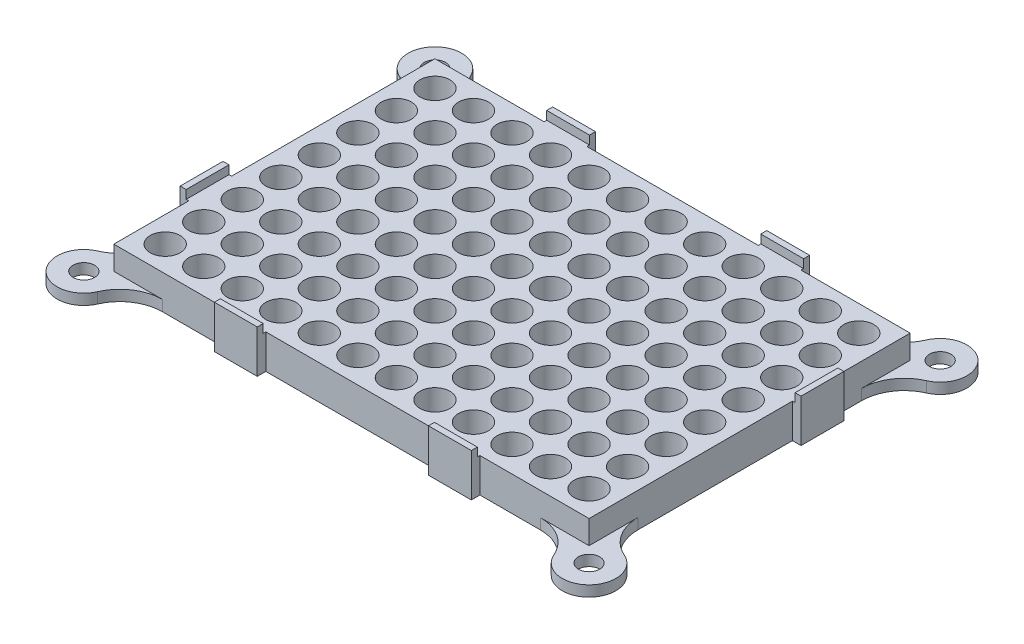
SolidWorks part; units mm, degrees
ref_plane "Front Plane" through (0, 0, 0) normal (0, 0, 1) x (1, 0, 0)
ref_plane "Top Plane" through (0, 0, 0) normal (0, 1, 0) x (1, 0, 0)
ref_plane "Right Plane" through (0, 0, 0) normal (1, 0, 0) x (0, 0, -1)
sketch "Sketch3" plane through (0, 0, 0) normal (0, 1, 0) x (1, 0, 0)
  line L0 (64, 80.5) -> (64, 5.5) construction
  line L1 (8.5, 5.5) -> (119.5, 5.5)
  line L2 (8.5, 5.5) -> (8.5, 80.5)
  line L3 (8.5, 80.5) -> (119.5, 80.5)
  line L4 (119.5, 5.5) -> (119.5, 80.5)
  line L5 (8.5, 43) -> (119.5, 43) construction
  line L6 (14.5, 74.5) -> (113.5, 74.5) construction
  line L7 (113.5, 74.5) -> (113.5, 11.5) construction
  line L8 (113.5, 11.5) -> (14.5, 11.5) construction
  line L9 (14.5, 11.5) -> (14.5, 74.5) construction
  circle A0 centre (14.5, 74.5) radius 3.5
  circle A1 centre (23.5, 74.5) radius 3.5
  circle A2 centre (32.5, 74.5) radius 3.5
  circle A3 centre (41.5, 74.5) radius 3.5
  circle A4 centre (50.5, 74.5) radius 3.5
  circle A5 centre (59.5, 74.5) radius 3.5
  circle A6 centre (68.5, 74.5) radius 3.5
  circle A7 centre (77.5, 74.5) radius 3.5
  circle A8 centre (86.5, 74.5) radius 3.5
  circle A9 centre (95.5, 74.5) radius 3.5
  circle A10 centre (104.5, 74.5) radius 3.5
  circle A11 centre (113.5, 74.5) radius 3.5
  circle A12 centre (23.5, 65.5) radius 3.5
  circle A13 centre (32.5, 65.5) radius 3.5
  circle A14 centre (41.5, 65.5) radius 3.5
  circle A15 centre (50.5, 65.5) radius 3.5
  circle A16 centre (59.5, 65.5) radius 3.5
  circle A17 centre (68.5, 65.5) radius 3.5
  circle A18 centre (77.5, 65.5) radius 3.5
  circle A19 centre (86.5, 65.5) radius 3.5
  circle A20 centre (95.5, 65.5) radius 3.5
  circle A21 centre (104.5, 65.5) radius 3.5
  circle A22 centre (113.5, 65.5) radius 3.5
  circle A23 centre (23.5, 56.5) radius 3.5
  circle A24 centre (32.5, 56.5) radius 3.5
  circle A25 centre (41.5, 56.5) radius 3.5
  circle A26 centre (50.5, 56.5) radius 3.5
  circle A27 centre (59.5, 56.5) radius 3.5
  circle A28 centre (68.5, 56.5) radius 3.5
  circle A29 centre (77.5, 56.5) radius 3.5
  circle A30 centre (86.5, 56.5) radius 3.5
  circle A31 centre (95.5, 56.5) radius 3.5
  circle A32 centre (104.5, 56.5) radius 3.5
  circle A33 centre (113.5, 56.5) radius 3.5
  circle A34 centre (23.5, 47.5) radius 3.5
  circle A35 centre (32.5, 47.5) radius 3.5
  circle A36 centre (41.5, 47.5) radius 3.5
  circle A37 centre (50.5, 47.5) radius 3.5
  circle A38 centre (59.5, 47.5) radius 3.5
  circle A39 centre (68.5, 47.5) radius 3.5
  circle A40 centre (77.5, 47.5) radius 3.5
  circle A41 centre (86.5, 47.5) radius 3.5
  circle A42 centre (95.5, 47.5) radius 3.5
  circle A43 centre (104.5, 47.5) radius 3.5
  circle A44 centre (113.5, 47.5) radius 3.5
  circle A45 centre (23.5, 38.5) radius 3.5
  circle A46 centre (32.5, 38.5) radius 3.5
  circle A47 centre (41.5, 38.5) radius 3.5
  circle A48 centre (50.5, 38.5) radius 3.5
  circle A49 centre (59.5, 38.5) radius 3.5
  circle A50 centre (68.5, 38.5) radius 3.5
  circle A51 centre (77.5, 38.5) radius 3.5
  circle A52 centre (86.5, 38.5) radius 3.5
  circle A53 centre (95.5, 38.5) radius 3.5
  circle A54 centre (104.5, 38.5) radius 3.5
  circle A55 centre (113.5, 38.5) radius 3.5
  circle A56 centre (23.5, 29.5) radius 3.5
  circle A57 centre (32.5, 29.5) radius 3.5
  circle A58 centre (41.5, 29.5) radius 3.5
  circle A59 centre (50.5, 29.5) radius 3.5
  circle A60 centre (59.5, 29.5) radius 3.5
  circle A61 centre (68.5, 29.5) radius 3.5
  circle A62 centre (77.5, 29.5) radius 3.5
  circle A63 centre (86.5, 29.5) radius 3.5
  circle A64 centre (95.5, 29.5) radius 3.5
  circle A65 centre (104.5, 29.5) radius 3.5
  circle A66 centre (113.5, 29.5) radius 3.5
  circle A67 centre (23.5, 20.5) radius 3.5
  circle A68 centre (32.5, 20.5) radius 3.5
  circle A69 centre (41.5, 20.5) radius 3.5
  circle A70 centre (50.5, 20.5) radius 3.5
  circle A71 centre (59.5, 20.5) radius 3.5
  circle A72 centre (68.5, 20.5) radius 3.5
  circle A73 centre (77.5, 20.5) radius 3.5
  circle A74 centre (86.5, 20.5) radius 3.5
  circle A75 centre (95.5, 20.5) radius 3.5
  circle A76 centre (104.5, 20.5) radius 3.5
  circle A77 centre (113.5, 20.5) radius 3.5
  circle A78 centre (23.5, 11.5) radius 3.5
  circle A79 centre (32.5, 11.5) radius 3.5
  circle A80 centre (41.5, 11.5) radius 3.5
  circle A81 centre (50.5, 11.5) radius 3.5
  circle A82 centre (59.5, 11.5) radius 3.5
  circle A83 centre (68.5, 11.5) radius 3.5
  circle A84 centre (77.5, 11.5) radius 3.5
  circle A85 centre (86.5, 11.5) radius 3.5
  circle A86 centre (95.5, 11.5) radius 3.5
  circle A87 centre (104.5, 11.5) radius 3.5
  circle A88 centre (113.5, 11.5) radius 3.5
  circle A89 centre (14.5, 65.5) radius 3.5
  circle A90 centre (14.5, 56.5) radius 3.5
  circle A91 centre (14.5, 47.5) radius 3.5
  circle A92 centre (14.5, 38.5) radius 3.5
  circle A93 centre (14.5, 29.5) radius 3.5
  circle A94 centre (14.5, 20.5) radius 3.5
  circle A95 centre (14.5, 11.5) radius 3.5
  dimension "D3" = 7
  dimension "D6" = 6
  dimension "D1" = 111
  dimension "D2" = 75
  dimension "D7" = 6
  dimension "D8" = 5.5
  dimension "D9" = 8.5
  dimension "D4" = 12
  dimension "D5" = 8
extrude "Well light guide" add sketch "Sketch3" along normal blind 8
sketch "Sketch1" plane through (0, 0, 0) normal (0, 1, 0) x (1, 0, 0)
  line L0 (8.5, 5.5) -> (119.5, 5.5) construction
  line L1 (5, 2) -> (123, 2) construction
  line L2 (5, 2) -> (5, 84) construction
  line L3 (5, 84) -> (123, 84) construction
  line L4 (123, 2) -> (123, 84) construction
  line L9 (8.5, 80.5) -> (8.5, 5.5) construction
  line L10 (64, 84) -> (64, 2) construction
  line L11 (5, 43) -> (123, 43) construction
  line L12 (119.5, 80.5) -> (8.5, 80.5) construction
  line L13 (119.5, 5.5) -> (119.5, 80.5) construction
  line L14 (8.5, 5.5) -> (119.5, 5.5) construction
  line L15 (8.5, 80.5) -> (8.5, 5.5) construction
  line L16 (119.5, 80.5) -> (8.5, 80.5) construction
  line L17 (119.5, 5.5) -> (119.5, 80.5) construction
  line L18 (116.75, 84) -> (116.75, 80.5)
  line L19 (123, 77.75) -> (119.5, 77.75)
  line L20 (119.5, 77.75) -> (119.5, 80.5)
  line L21 (119.5, 80.5) -> (116.75, 80.5)
  line L22 (11.25, 84) -> (11.25, 80.5)
  line L23 (8.5, 80.5) -> (11.25, 80.5)
  line L24 (8.5, 77.75) -> (8.5, 80.5)
  line L25 (5, 77.75) -> (8.5, 77.75)
  line L26 (11.25, 2) -> (11.25, 5.5)
  line L27 (8.5, 5.5) -> (11.25, 5.5)
  line L28 (8.5, 8.25) -> (8.5, 5.5)
  line L29 (5, 8.25) -> (8.5, 8.25)
  line L30 (119.5, 5.5) -> (116.75, 5.5)
  line L31 (119.5, 8.25) -> (119.5, 5.5)
  line L32 (123, 8.25) -> (119.5, 8.25)
  line L33 (116.75, 2) -> (116.75, 5.5)
  arc A0 (123, 77.75) -> (116.75, 84) centre (123, 84) ccw
  arc A1 (5, 77.75) -> (11.25, 84) centre (5, 84) cw
  arc A2 (5, 8.25) -> (11.25, 2) centre (5, 2) ccw
  arc A3 (123, 8.25) -> (116.75, 2) centre (123, 2) cw
  circle A4 centre (123, 84) radius 2.5
  circle A5 centre (5, 84) radius 2.5
  circle A6 centre (5, 2) radius 2.5
  circle A7 centre (123, 2) radius 2.5
  point P9 (64, 5.5)
  point P10 (119.5, 43)
  dimension "D3" = 6.25
  dimension "D4" = 5
  dimension "D1" = 118
  dimension "D2" = 82
extrude "PCB mount plate" add sketch "Sketch1" along normal blind 2.5
sketch "Sketch4" plane through (0, 0, 0) normal (0, -1, 0) x (1, 0, 0)
  line L0 (5, -43) -> (123, -43) construction
  line L1 (44, -80.5) -> (34, -80.5)
  line L2 (44, -80.5) -> (44, -82.5)
  line L3 (44, -82.5) -> (34, -82.5)
  line L4 (34, -80.5) -> (34, -82.5)
  line L5 (64, -84) -> (64, -2) construction
  line L6 (5, -43) -> (123, -43) construction
  line L7 (64, -84) -> (64, -2) construction
  line L8 (119.5, -80.5) -> (8.5, -80.5) construction
  line L9 (84, -5.5) -> (84, -3.5)
  line L10 (94, -5.5) -> (84, -5.5)
  line L11 (94, -5.5) -> (94, -3.5)
  line L12 (94, -3.5) -> (84, -3.5)
  line L13 (8.5, -80.5) -> (8.5, -5.5) construction
  line L14 (8.5, -33) -> (6.5, -33)
  line L15 (8.5, -33) -> (8.5, -23)
  line L16 (8.5, -23) -> (6.5, -23)
  line L17 (6.5, -33) -> (6.5, -23)
  line L18 (119.5, -63) -> (121.5, -63)
  line L19 (119.5, -63) -> (119.5, -53)
  line L20 (119.5, -53) -> (121.5, -53)
  line L21 (121.5, -63) -> (121.5, -53)
  line L22 (119.5, -5.5) -> (119.5, -80.5) construction
  line L23 (8.5, -5.5) -> (119.5, -5.5) construction
  line L24 (34, -5.5) -> (44, -5.5)
  line L25 (34, -5.5) -> (34, -3.5)
  line L26 (34, -3.5) -> (44, -3.5)
  line L27 (44, -5.5) -> (44, -3.5)
  line L28 (84, -82.5) -> (94, -82.5)
  line L29 (94, -80.5) -> (94, -82.5)
  line L30 (84, -80.5) -> (94, -80.5)
  line L31 (84, -80.5) -> (84, -82.5)
  dimension "D1" = 2
  dimension "D2" = 10
  dimension "D3" = 2
  dimension "D4" = 10
  dimension "D5" = 10
  dimension "D6" = 10
  dimension "D7" = 2
  dimension "D8" = 10
  dimension "D9" = 20
  dimension "D10" = 10
  dimension "D11" = 2
  dimension "D12" = 20
extrude "Top guide tabs" add sketch "Sketch4" against normal blind 10
sketch "Sketch5" plane through (0, 8, 0) normal (0, 1, 0) x (1, 0, 0)
  line L0 (64, 84) -> (64, 2) construction
  line L1 (84, 5.5) -> (94, 5.5) construction
  line L2 (84, 5.5) -> (94, 5.5) construction
  line L7 (84, 80.5) -> (84, 81.1)
  line L8 (84, 5.5) -> (94, 5.5)
  line L9 (5, 43) -> (123, 43) construction
  line L10 (64, 84) -> (64, 2) construction
  line L11 (5, 43) -> (123, 43) construction
  line L12 (84, 5.5) -> (84, 4.9)
  line L14 (84, 4.9) -> (94, 4.9)
  line L15 (94, 5.5) -> (94, 4.9)
  line L16 (94, 80.5) -> (94, 81.1)
  line L21 (84, 81.1) -> (94, 81.1)
  line L22 (84, 80.5) -> (94, 80.5)
  line L23 (119.5, 53) -> (119.5, 63) construction
  line L24 (119.5, 63) -> (120.1, 63)
  line L25 (119.5, 63) -> (119.5, 53)
  line L26 (119.5, 53) -> (120.1, 53)
  line L27 (120.1, 63) -> (120.1, 53)
  line L28 (119.5, 53) -> (119.5, 63) construction
  line L33 (34, 80.5) -> (34, 81.1)
  line L34 (44, 80.5) -> (34, 80.5)
  line L35 (44, 80.5) -> (44, 81.1)
  line L36 (44, 81.1) -> (34, 81.1)
  line L37 (34, 5.5) -> (34, 4.9)
  line L38 (44, 5.5) -> (34, 5.5)
  line L39 (44, 4.9) -> (34, 4.9)
  line L40 (44, 5.5) -> (44, 4.9)
  line L41 (8.5, 33) -> (8.5, 23)
  line L46 (8.5, 23) -> (7.9, 23)
  line L47 (7.9, 23) -> (7.9, 33)
  line L48 (7.9, 33) -> (8.5, 33)
  point P6 (89, 5.5)
  point P19 (119.5, 58)
  dimension "D1" = 0.6
  dimension "D2" = 0.6
  dimension "D3" = 0.6
extrude "3Dprint spacer" cut sketch "Sketch5" along normal through all
fillet "Fillet1" radius 10 8 edges at (116.75, 1.25, -80.5) (119.5, 1.25, -77.75) (119.5, 1.25, -8.25) (116.75, 1.25, -5.5) (11.25, 1.25, -5.5) (8.5, 1.25, -8.25) (11.25, 1.25, -80.5) (8.5, 1.25, -77.75)
